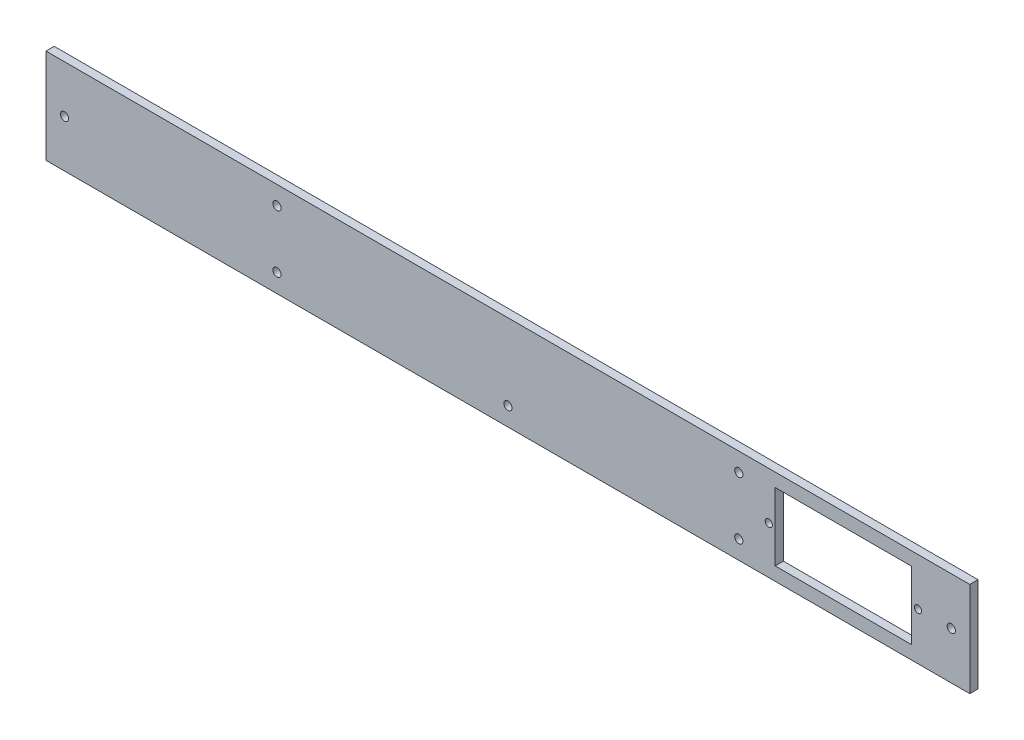
SolidWorks part; units mm, degrees
ref_plane "Piano frontale" through (0, 0, 0) normal (0, 0, 1) x (1, 0, 0)
ref_plane "Piano superiore" through (0, 0, 0) normal (0, 1, 0) x (1, 0, 0)
ref_plane "Piano destro" through (0, 0, 0) normal (1, 0, 0) x (0, 0, -1)
sketch "Schizzo1" plane through (0, 0, 0) normal (0, 0, 1) x (1, 0, 0)
  line L0 (0, 0) -> (0, 46)
  line L1 (0, 46) -> (449, 46)
  line L2 (449, 46) -> (449, 0)
  line L3 (449, 0) -> (0, 0)
  line L4 (0, 23) -> (449, 23) construction
  line L5 (224.5, 42) -> (224.5, 123.488) construction
  line L6 (0, 0) -> (224.5, 46) construction
  line L7 (112.25, 23) -> (112.25, 46) construction
  line L8 (387.5639, 23) -> (387.5639, 39.5) construction
  line L9 (420.7139, 6.5) -> (354.4139, 6.5)
  line L10 (420.7139, 6.5) -> (420.7139, 39.5)
  line L11 (420.7139, 39.5) -> (354.4139, 39.5)
  line L12 (354.4139, 6.5) -> (354.4139, 39.5)
  line L13 (420.7139, 6.5) -> (354.4139, 39.5) construction
  line L14 (420.7139, 39.5) -> (354.4139, 6.5) construction
  circle A0 centre (9, 23) radius 2
  circle A1 centre (112.25, 37) radius 2
  circle A2 centre (224.5, 9) radius 2
  circle A3 centre (440, 23) radius 2
  circle A4 centre (336.75, 37) radius 2
  circle A5 centre (423.8139, 23) radius 1.75
  circle A6 centre (351.3139, 23) radius 1.75
  circle A7 centre (336.75, 9) radius 2
  circle A8 centre (112.25, 9) radius 2
  point P22 (387.5639, 23)
  dimension "D3" = 9
  dimension "D4" = 9
  dimension "D6" = 4
  dimension "D5" = 4
  dimension "D8" = 4
  dimension "D9" = 4
  dimension "D14" = 3.5
  dimension "D1" = 46
  dimension "D2" = 449
  dimension "D7" = 9
  dimension "D10" = 9
  dimension "D11" = 66.3
  dimension "D12" = 33
  dimension "D13" = 36.25
extrude "Estrusione-Estrusione1" add sketch "Schizzo1" along normal blind 4
